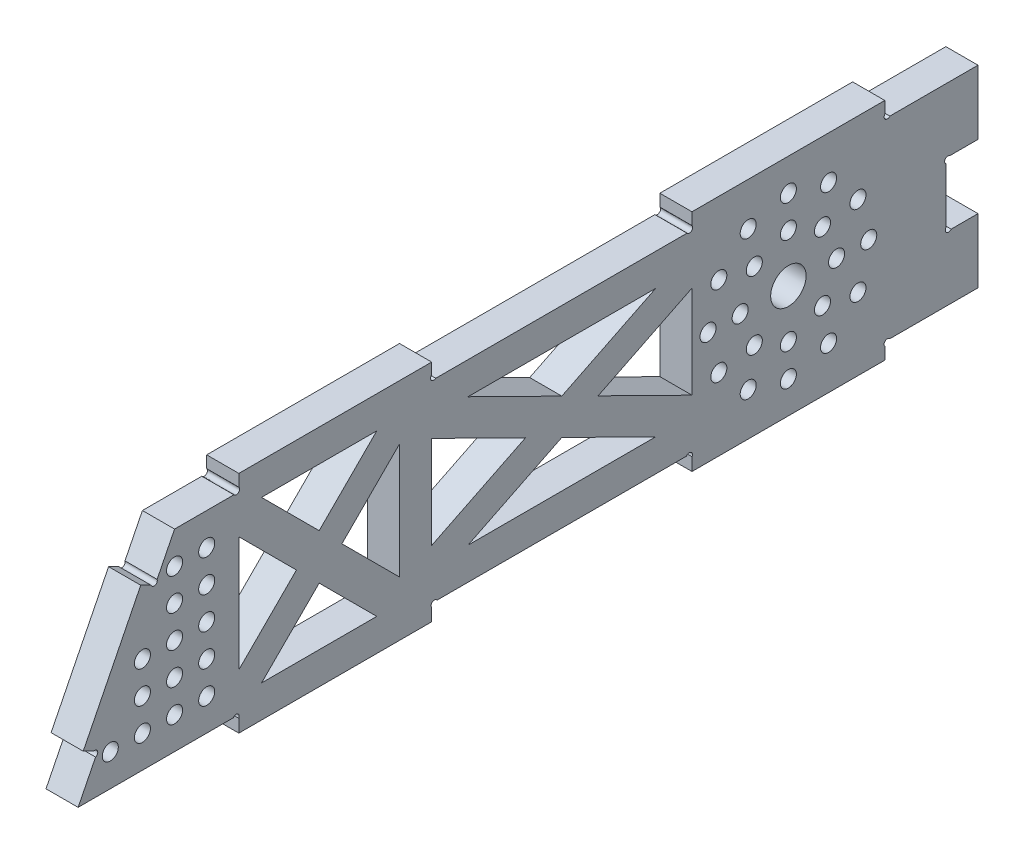
SolidWorks part; units mm, degrees
material "7050-T73510"
ref_plane "Front Plane" through (0, 0, 0) normal (0, 0, 1) x (1, 0, 0)
ref_plane "Top Plane" through (0, 0, 0) normal (0, 1, 0) x (1, 0, 0)
ref_plane "Right Plane" through (0, 0, 0) normal (1, 0, 0) x (0, 0, -1)
sketch "Sketch1" plane through (0, 0, 0) normal (1, 0, 0) x (0, 0, -1)
  line L1 (-177.8, -38.1) -> (177.8, -38.1)
  line L2 (-177.8, -38.1) -> (-177.8, 38.1)
  line L3 (-177.8, 38.1) -> (177.8, 38.1)
  line L4 (177.8, -38.1) -> (177.8, 38.1)
  line L5 (-177.8, -38.1) -> (177.8, 38.1) construction
  line L6 (-177.8, 38.1) -> (177.8, -38.1) construction
  point P0 (0, 0)
  dimension "D1" = 355.6
  dimension "D2" = 76.2
extrude "Boss-Extrude1" add sketch "Sketch1" along normal blind 12.7
sketch "Sketch2" plane through (12.7, 0, 0) normal (1, 0, 0) x (0, 0, -1)
  line L0 (-177.8, -38.1) -> (-139.7, 38.1)
  line L1 (177.8, 38.1) -> (-177.8, 38.1) construction
  dimension "D1" = 38.1
extrude "Cut-Extrude1" cut sketch "Sketch2" against normal through all and the other way through all
sketch "Sketch3" plane through (0, 0, 0) normal (-1, 0, 0) x (0, 0, 1)
  line L0 (177.8, -38.1) -> (-177.8, -38.1) construction
  line L1 (-140.97, -38.1) -> (-64.77, -38.1)
  line L2 (-140.97, -38.1) -> (-140.97, -44.45)
  line L3 (-140.97, -44.45) -> (-64.77, -44.45)
  line L4 (-64.77, -38.1) -> (-64.77, -44.45)
  line L5 (-177.8, -38.1) -> (-177.8, 38.1) construction
  line L6 (38.1, -38.1) -> (114.3, -38.1)
  line L7 (38.1, -38.1) -> (38.1, -44.45)
  line L8 (38.1, -44.45) -> (114.3, -44.45)
  line L9 (114.3, -38.1) -> (114.3, -44.45)
  line L10 (-177.8, 38.1) -> (139.7, 38.1) construction
  line L11 (-140.97, 38.1) -> (-64.77, 38.1)
  line L12 (-140.97, 38.1) -> (-140.97, 44.45)
  line L13 (-140.97, 44.45) -> (-64.77, 44.45)
  line L14 (-64.77, 38.1) -> (-64.77, 44.45)
  line L16 (38.1, 38.1) -> (114.3, 38.1)
  line L17 (38.1, 38.1) -> (38.1, 44.45)
  line L18 (38.1, 44.45) -> (114.3, 44.45)
  line L19 (114.3, 38.1) -> (114.3, 44.45)
  dimension "D1" = 76.2
  dimension "D2" = 6.35
  dimension "D3" = 76.2
  dimension "D4" = 6.35
  dimension "D5" = 36.83
  dimension "D6" = 215.9
  dimension "D7" = 76.2
  dimension "D8" = 6.35
  dimension "D9" = 6.35
  dimension "D10" = 76.2
extrude "Boss-Extrude2" add sketch "Sketch3" against normal blind 12.7
sketch "Sketch4" plane through (0, 0, 0) normal (-1, 0, 0) x (0, 0, 1)
  line L0 (-177.8, -38.1) -> (-177.8, 38.1) construction
  line L1 (-177.8, 12.7) -> (-165.1, 12.7)
  line L2 (-177.8, 12.7) -> (-177.8, -12.7)
  line L3 (-177.8, -12.7) -> (-165.1, -12.7)
  line L4 (-165.1, 12.7) -> (-165.1, -12.7)
  line L5 (-140.97, -38.1) -> (-177.8, -38.1) construction
  line L6 (-177.8, 38.1) -> (-140.97, 38.1) construction
  dimension "D1" = 25.4
  dimension "D2" = 25.4
  dimension "D3" = 12.7
extrude "Cut-Extrude2" cut sketch "Sketch4" against normal through all
sketch "Sketch5" plane through (0, 0, 0) normal (-1, 0, 0) x (0, 0, 1)
  line L0 (-165.1, -12.7) -> (-165.1, 12.7) construction
  line L1 (-140.97, -38.1) -> (-177.8, -38.1) construction
  circle A0 centre (-102.87, 0) radius 7
  dimension "D1" = 62.23
  dimension "D3" = 14
  dimension "D2" = 38.1
extrude "Cut-Extrude3" cut sketch "Sketch5" against normal through all
sketch "Sketch6" plane through (0, 0, 0) normal (-1, 0, 0) x (0, 0, 1)
  line L0 (38.1, -38.1) -> (-64.77, -38.1) construction
  line L1 (-64.77, 25.4) -> (38.1, 25.4)
  line L2 (-64.77, 25.4) -> (-64.77, -25.4)
  line L3 (-64.77, -25.4) -> (38.1, -25.4)
  line L4 (38.1, 25.4) -> (38.1, -25.4)
  line L5 (-64.77, 38.1) -> (38.1, 38.1) construction
  line L6 (38.1, 44.45) -> (38.1, 38.1) construction
  line L7 (-64.77, 38.1) -> (-64.77, 44.45) construction
  line L8 (-64.77, 25.4) -> (38.1, -25.4) construction
  line L9 (-64.77, -25.4) -> (38.1, 25.4) construction
  line L10 (-50.4288, -25.4) -> (-13.335, -7.0821)
  line L11 (23.7588, 25.4) -> (-13.335, 7.0821)
  line L12 (-50.4288, 25.4) -> (-13.335, 7.0821)
  line L13 (23.7588, -25.4) -> (-13.335, -7.0821)
  line L14 (1.0062, 0) -> (38.1, 18.3179)
  line L15 (-27.6762, 0) -> (-64.77, 18.3179)
  line L16 (1.0062, 0) -> (38.1, -18.3179)
  line L17 (-27.6762, 0) -> (-64.77, -18.3179)
  line L18 (38.1, -44.45) -> (114.3, -44.45) construction
  line L19 (50.8, 31.75) -> (114.3, 31.75)
  line L20 (50.8, 31.75) -> (50.8, -31.75)
  line L21 (50.8, -31.75) -> (114.3, -31.75)
  line L22 (114.3, 31.75) -> (114.3, -31.75)
  line L23 (114.3, 44.45) -> (38.1, 44.45) construction
  line L26 (114.3, 38.1) -> (114.3, 44.45) construction
  line L28 (50.8, -31.75) -> (114.3, 31.75) construction
  line L29 (114.3, -31.75) -> (50.8, 31.75) construction
  line L30 (59.7803, -31.75) -> (114.3, 22.7697)
  line L31 (50.8, -22.7697) -> (105.3197, 31.75)
  line L32 (114.3, -22.7697) -> (59.7803, 31.75)
  line L33 (105.3197, -31.75) -> (50.8, 22.7697)
  point P36 (114.3, 41.275)
  dimension "D1" = 12.7
  dimension "D2" = 12.7
  dimension "D3" = 12.7
  dimension "D4" = 12.7
  dimension "D5" = 12.7
  dimension "D6" = 12.7
  dimension "D7" = 12.7
  dimension "D8" = 0
  dimension "D9" = 12.7
  dimension "D10" = 12.7
extrude "Cut-Extrude4" cut sketch "Sketch6" against normal through all contours L3 L13 L10 | L17 L15 L2 | L1 L12 L11 | L14 L16 L4 | L21 L33 L30 | L32 L22 L30 | L31 L33 L20 | L32 L31 L19 region at (0, 19.294, -13.335) region at (0, 0, -52.4054) region at (0, 0, 25.7354) region at (0, -19.294, -13.335) region at (0, 24.1601, 82.55) region at (0, 0, 58.3899) region at (0, 0, 106.7101) region at (0, -24.1601, 82.55)
sketch "Sketch8" plane through (12.7, 0, 0) normal (1, 0, 0) x (0, 0, -1)
  line L0 (-147.3908, 22.7185) -> (-170.1092, -22.7185)
  line L1 (-147.3908, 22.7185) -> (-153.0704, 25.5583)
  line L2 (-170.1092, -22.7185) -> (-175.7888, -19.8786)
  line L3 (-153.0704, 25.5583) -> (-175.7888, -19.8786)
  line L4 (-177.8, -38.1) -> (-139.7, 38.1) construction
  line L5 (-158.75, 0) -> (-181.9472, 11.5986) construction
  dimension "D1" = 6.35
  dimension "D2" = 50.8
extrude "Boss-Extrude3" add sketch "Sketch8" against normal blind 12.7
sketch "Sketch7" plane through (12.7, 0, 0) normal (1, 0, 0) x (0, 0, -1)
  line L0 (-114.3, 38.1) -> (-139.7, 38.1) construction
  line L2 (-114.3, 22.7697) -> (-114.3, -22.7697) construction
  circle A0 centre (121.92, 0) radius 3.175
  circle A1 centre (102.87, 0) radius 7 construction
  circle A2 centre (134.62, 0) radius 3.175
  circle A3 centre (116.3404, -13.4704) radius 3.175
  circle A4 centre (102.87, -19.05) radius 3.175
  circle A5 centre (89.3996, -13.4704) radius 3.175
  circle A6 centre (83.82, 0) radius 3.175
  circle A7 centre (89.3996, 13.4704) radius 3.175
  circle A8 centre (102.87, 19.05) radius 3.175
  circle A9 centre (116.3404, 13.4704) radius 3.175
  circle A10 centre (130.3663, -15.875) radius 3.175
  circle A11 centre (118.745, -27.4963) radius 3.175
  circle A12 centre (102.87, -31.75) radius 3.175
  circle A13 centre (86.995, -27.4963) radius 3.175
  circle A14 centre (75.3737, -15.875) radius 3.175
  circle A15 centre (71.12, 0) radius 3.175
  circle A16 centre (75.3737, 15.875) radius 3.175
  circle A17 centre (86.995, 27.4963) radius 3.175
  circle A18 centre (102.87, 31.75) radius 3.175
  circle A19 centre (118.745, 27.4963) radius 3.175
  circle A20 centre (130.3663, 15.875) radius 3.175
  circle A21 centre (-127, 25.4) radius 3.175
  circle A22 centre (-127, 12.7) radius 3.175
  circle A23 centre (-127, 0) radius 3.175
  circle A24 centre (-127, -12.7) radius 3.175
  circle A25 centre (-127, -25.4) radius 3.175
  circle A26 centre (-139.7, 12.7) radius 3.175
  circle A27 centre (-139.7, 0) radius 3.175
  circle A28 centre (-139.7, -12.7) radius 3.175
  circle A29 centre (-139.7, -25.4) radius 3.175
  circle A31 centre (-152.4, 0) radius 3.175
  circle A32 centre (-152.4, -12.7) radius 3.175
  circle A33 centre (-152.4, -25.4) radius 3.175
  circle A37 centre (-165.1, -25.4) radius 3.175
  circle A38 centre (-139.7, 25.4) radius 3.175
  circle A41 centre (-165.1, 25.4) radius 3.175 [skipped]
  circle A42 centre (-152.4, 25.4) radius 3.175 [skipped]
  circle A43 centre (-152.4, 12.7) radius 3.175 [skipped]
  circle A44 centre (-165.1, 0) radius 3.175 [skipped]
  circle A45 centre (-165.1, -12.7) radius 3.175 [skipped]
  circle A46 centre (-165.1, 12.7) radius 3.175 [skipped]
  point P22 (102.87, 0)
  point P46 (102.87, 0)
  dimension "D1" = 6.35
  dimension "D3" = 6.35
  dimension "D7" = 12.7
  dimension "D2" = 19.05
  dimension "D4" = 12.7
  dimension "D8" = 12.7
  dimension "D9" = 5
  dimension "D10" = 4
  dimension "D5" = 8
  dimension "D6" = 12
extrude "Cut-Extrude5" cut sketch "Sketch7" against normal through all
sketch "Sketch9" plane through (0, 0, 0) normal (-1, 0, 0) x (0, 0, 1)
  line L0 (147.3908, 22.7185) -> (155.6395, 47.4646) construction
  line L1 (170.1092, -22.7185) -> (188.3232, -28.7898) construction
  line L2 (147.3908, 22.7185) -> (153.0704, 25.5583) construction
  line L3 (175.7888, -19.8786) -> (170.1092, -22.7185) construction
  circle A0 centre (-165.8862, 11.7026) radius 1.27
  circle A1 centre (-166.1424, -11.9745) radius 1.27
  circle A2 centre (-141.9722, 38.88) radius 1.27
  circle A3 centre (-141.9651, -38.8891) radius 1.27
  circle A4 centre (-63.6683, -38.7317) radius 1.27
  circle A5 centre (-63.7916, 38.9097) radius 1.27
  circle A6 centre (37.2908, 39.0788) radius 1.27
  circle A7 centre (37.0294, -38.7832) radius 1.27
  circle A8 centre (115.4028, -38.7299) radius 1.27
  circle A9 centre (115.2731, 38.916) radius 1.27
  circle A10 centre (147.7924, 23.9233) radius 1.27
  circle A11 centre (171.3141, -23.1201) radius 1.27
  dimension "D1" = 45
  dimension "D2" = 45
extrude "Cut-Extrude6" cut sketch "Sketch9" against normal through all
